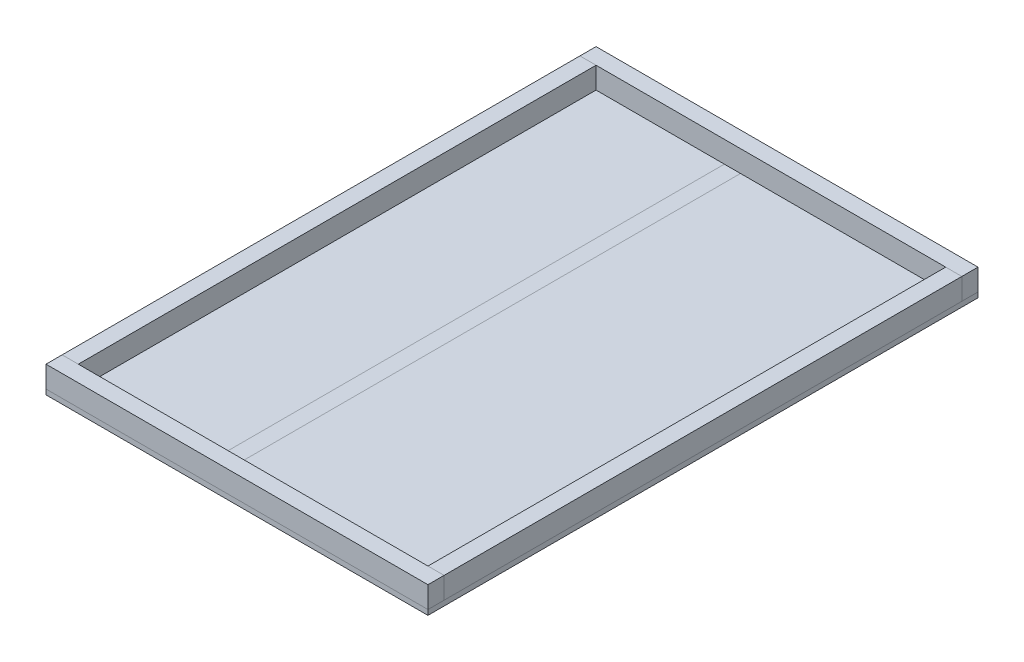
SolidWorks part; units mm, degrees
material "Oak"
ref_plane "Front Plane" through (0, 0, 0) normal (0, 0, 1) x (1, 0, 0)
ref_plane "Top Plane" through (0, 0, 0) normal (0, 1, 0) x (1, 0, 0)
ref_plane "Right Plane" through (0, 0, 0) normal (1, 0, 0) x (0, 0, -1)
sketch "Sketch1" plane through (0, 0, 0) normal (0, 1, 0) x (1, 0, 0)
  line L0 (206.35, 305.55) -> (225.4, 305.55)
  line L1 (-225.4, -324.6) -> (225.4, -324.6)
  line L2 (-225.4, -324.6) -> (-225.4, 324.6)
  line L3 (-225.4, 324.6) -> (225.4, 324.6)
  line L4 (225.4, -324.6) -> (225.4, 324.6)
  line L5 (-225.4, -324.6) -> (225.4, 324.6) construction
  line L6 (-225.4, 324.6) -> (225.4, -324.6) construction
  line L7 (-206.35, -305.55) -> (206.35, -305.55)
  line L8 (-206.35, -305.55) -> (-206.35, 305.55)
  line L9 (-206.35, 305.55) -> (206.35, 305.55)
  line L10 (206.35, -305.55) -> (206.35, 305.55)
  line L11 (-206.35, -305.55) -> (206.35, 305.55) construction
  line L12 (-206.35, 305.55) -> (206.35, -305.55) construction
  line L13 (-206.35, 305.55) -> (-225.4, 305.55)
  line L14 (-206.35, -305.55) -> (-225.4, -305.55)
  line L15 (206.35, -305.55) -> (225.4, -305.55)
  point P0 (0, 0)
  point P6 (0, 0)
  dimension "D1" = 450.8
  dimension "D2" = 649.2
  dimension "D3" = 19.05
  dimension "D4" = 19.05
extrude "Boss-Extrude1" add sketch "Sketch1" against normal blind 6 contours L14 L8 L13 L2 | L13 L9 L0 L4 L3 L2 | L7 L10 L9 L8 | L10 L15 L4 L0 | L15 L7 L14 L2 L1 L4 | L3 L4 L1 L2 region at (0, 0, -315.075) region at (0, 0, 0) region at (215.875, 0, 0) region at (-215.875, 0, 0) region at (0, 0, 315.075)
extrude "Boss-Extrude2" add sketch "Sketch1<3>" along normal blind 25.4 separate body contours L14 L8 L13 L2 | L10 L15 L4 L0 region at (215.875, 0, 0) region at (-215.875, 0, 0)
sketch "Sketch1<3>" plane through (0, 0, 0) normal (0, 1, 0) x (1, 0, 0) same geometry as "Sketch1"
extrude "Boss-Extrude3" add sketch "Sketch1<4>" along normal blind 25.4 separate body contours L13 L9 L0 L4 L3 L2 | L15 L7 L14 L2 L1 L4 region at (0, 0, -315.075) region at (0, 0, 315.075)
sketch "Sketch1<4>" plane through (0, 0, 0) normal (0, 1, 0) x (1, 0, 0) same geometry as "Sketch1"
sketch "Sketch4" plane through (0, -6, 0) normal (0, -1, 0) x (1, 0, 0)
  line L0 (225.4, -305.55) -> (-225.4, -305.55) construction
  line L1 (-225.4, 305.55) -> (225.4, 305.55) construction
  line L2 (225.4, -305.55) -> (-225.4, -305.55) construction
  line L3 (-225.4, 305.55) -> (225.4, 305.55) construction
  line L5 (-70.8, -305.55) -> (-20, -305.55)
  line L6 (-70.8, -305.55) -> (-70.8, 305.55)
  line L7 (-70.8, 305.55) -> (-20, 305.55)
  line L8 (-20, -305.55) -> (-20, 305.55)
  line L9 (-70.8, -305.55) -> (-20, 305.55) construction
  line L10 (-70.8, 305.55) -> (-20, -305.55) construction
  line L12 (-225.4, 324.6) -> (-225.4, -324.6) construction
  point P4 (-45.4, 0)
  point P9 (-52.1723, -259.184)
  dimension "D1" = 50.8
  dimension "D2" = 180
extrude "Boss-Extrude5" add sketch "Sketch4" along normal blind 19.05
sketch "Sketch2" plane through (0, 0, 0) normal (0, 1, 0) x (1, 0, 0)
  line L0 (-225.4, -305.55) -> (225.4, -305.55) construction
  line L1 (225.4, 305.55) -> (-225.4, 305.55) construction
  line L2 (-225.4, -305.55) -> (225.4, -305.55) construction
  line L3 (225.4, 305.55) -> (-225.4, 305.55) construction
  line L5 (-54.925, -305.55) -> (-35.875, -305.55)
  line L6 (-54.925, -305.55) -> (-54.925, 305.55)
  line L7 (-54.925, 305.55) -> (-35.875, 305.55)
  line L8 (-35.875, -305.55) -> (-35.875, 305.55)
  line L9 (-54.925, -305.55) -> (-35.875, 305.55) construction
  line L10 (-54.925, 305.55) -> (-35.875, -305.55) construction
  line L11 (-20, 305.55) -> (-20, -305.55) construction
  line L12 (-70.8, -305.55) -> (-70.8, 305.55) construction
  line L13 (-20, 305.55) -> (-20, -305.55) construction
  line L14 (-70.8, -305.55) -> (-70.8, 305.55) construction
  line L15 (-70.8, 0) -> (-45.4, 0) construction
  line L16 (-45.4, 0) -> (-20, 0) construction
  point P4 (-45.4, 0)
  dimension "D1" = 19.05
extrude "Cut-Extrude1" cut sketch "Sketch2" against normal blind 9.525
extrude "Boss-Extrude4" add sketch "Sketch2<2>" against normal blind 9.525 separate body
sketch "Sketch2<2>" plane through (0, 0, 0) normal (0, 1, 0) x (1, 0, 0) same geometry as "Sketch2"
